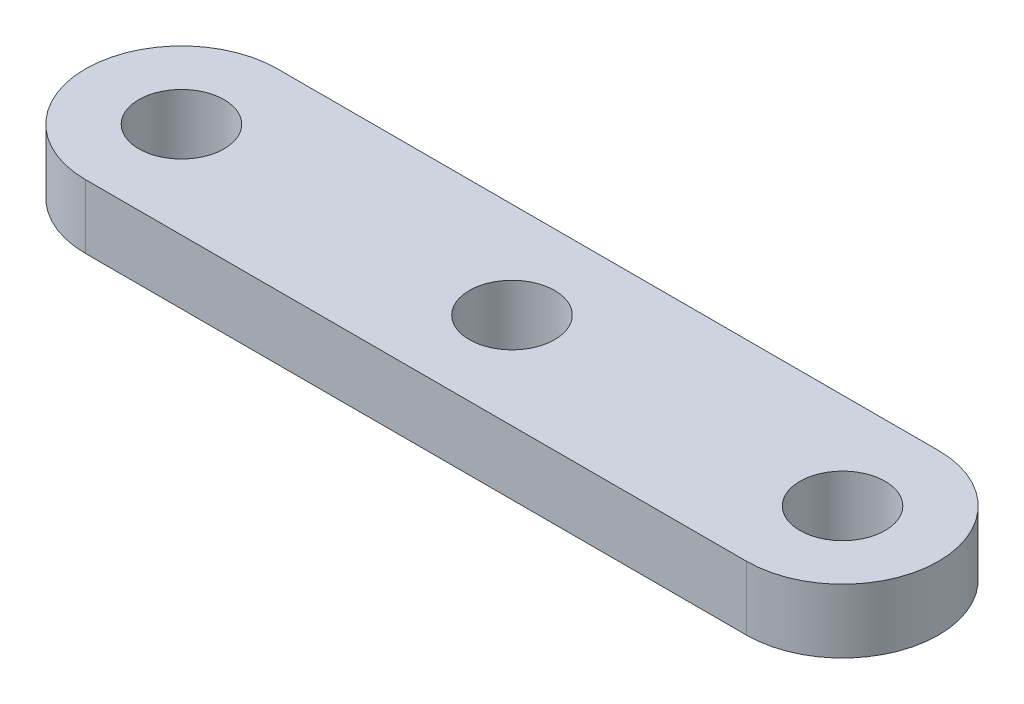
SolidWorks part; units mm, degrees
ref_plane "Front Plane" through (0, 0, 0) normal (0, 0, 1) x (1, 0, 0)
ref_plane "Top Plane" through (0, 0, 0) normal (0, 1, 0) x (1, 0, 0)
ref_plane "Right Plane" through (0, 0, 0) normal (1, 0, 0) x (0, 0, -1)
sketch "Sketch2" plane through (0, 0, 0) normal (0, 1, 0) x (1, 0, 0)
  line L1 (0, 0) -> (62, 0)
  line L3 (0, 18) -> (62, 18)
  arc A1 (0, 0) -> (0, 18) centre (0, 9) cw
  arc A2 (62, 0) -> (62, 18) centre (62, 9) ccw
  dimension "D1" = 18
  dimension "D2" = 62
extrude "Boss-Extrude1" add sketch "Sketch2" along normal blind 6
sketch "Sketch3" plane through (0, 0, 0) normal (0, -1, 0) x (1, 0, 0)
  line L0 (0, 0) -> (62, 0) construction
  line L1 (31, 0) -> (31, -18) construction
  line L2 (62, -18) -> (0, -18) construction
  circle A0 centre (0, -9) radius 4
  circle A1 centre (31, -9) radius 4
  circle A2 centre (62, -9) radius 4
  dimension "D1" = 9
  dimension "D2" = 8
extrude "Cut-Extrude1" cut sketch "Sketch3" against normal blind 6
